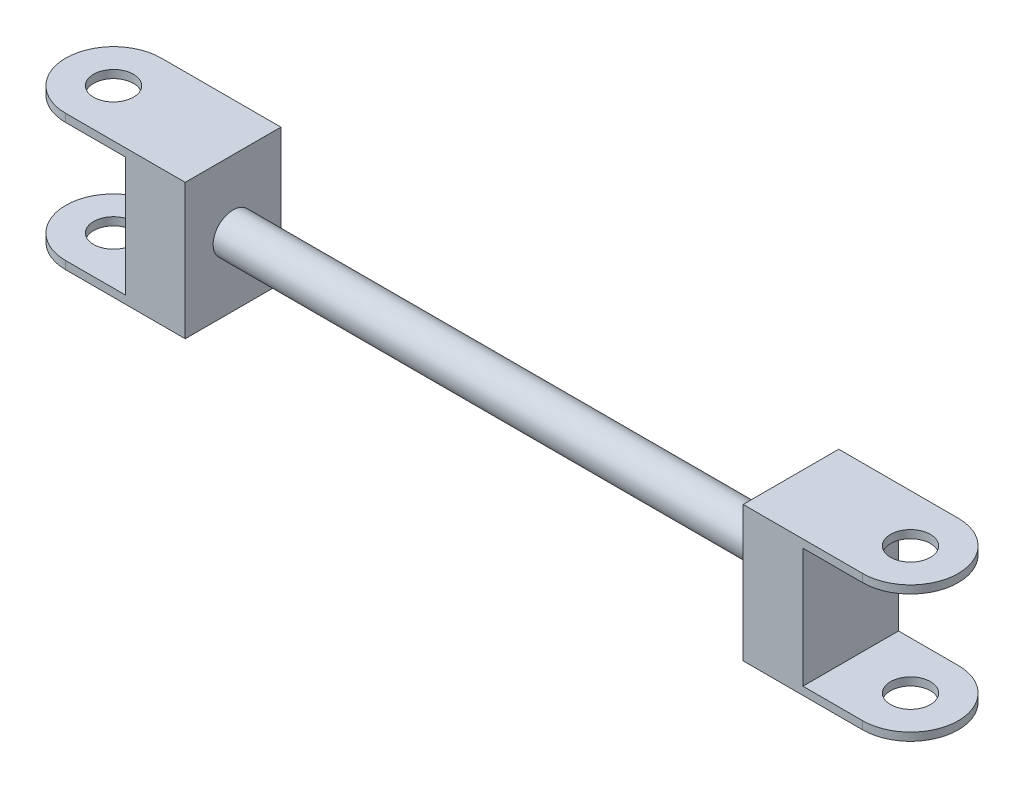
SolidWorks part; units mm, degrees
ref_plane "Front Plane" through (0, 0, 0) normal (0, 0, 1) x (1, 0, 0)
ref_plane "Top Plane" through (0, 0, 0) normal (0, 1, 0) x (1, 0, 0)
ref_plane "Right Plane" through (0, 0, 0) normal (1, 0, 0) x (0, 0, -1)
sketch "Sketch1" plane through (0, 0, 0) normal (0, 1, 0) x (1, 0, 0)
  line L1 (-69.1768, 12) -> (-39.1768, 12)
  line L3 (-69.1768, -12) -> (-39.1768, -12)
  line L4 (-39.1768, 12) -> (-39.1768, -12)
  line L5 (130.8232, 12) -> (100.8232, 12)
  line L7 (130.8232, -12) -> (100.8232, -12)
  line L8 (100.8232, 12) -> (100.8232, -12)
  circle A0 centre (-69.1768, 0) radius 5
  circle A1 centre (130.8232, 0) radius 5
  arc A2 (-69.1768, 12) -> (-69.1768, -12) centre (-69.1768, 0) ccw
  arc A3 (130.8232, -12) -> (130.8232, 12) centre (130.8232, 0) ccw
  dimension "D2" = 10
  dimension "D3" = 10
  dimension "D4" = 24
  dimension "D5" = 24
  dimension "D8" = 30
  dimension "D1" = 200
  dimension "D6" = 30
  dimension "D7" = 24
extrude "Boss-Extrude1" add sketch "Sketch1" along normal blind 17 and the other way blind 17 contours A2 L1 L4 L3 | A3 L5 L8 L7 | A0 | A1
sketch "Sketch3" plane through (-39.1768, 0, 0) normal (1, 0, 0) x (0, 0, -1)
  circle A0 centre (0, 0) radius 5
  dimension "D1" = 10
extrude "Boss-Extrude2" add sketch "Sketch3" along normal up to surface (140 mm away) up to face at (100.8232, 0, 0)
sketch "Sketch4" plane through (0, 0, 0) normal (0, 1, 0) x (1, 0, 0)
  line L0 (100.8232, -12) -> (130.8232, -12) construction
  line L1 (130.8232, 12) -> (100.8232, 12) construction
  line L3 (-69.1768, -12) -> (-39.1768, -12) construction
  line L5 (-39.1768, 12) -> (-69.1768, 12) construction
  line L6 (115.8232, -12) -> (130.8232, -12)
  line L7 (130.8232, 12) -> (115.8232, 12)
  line L9 (-69.1768, -12) -> (-54.1768, -12)
  line L11 (-54.1768, 12) -> (-69.1768, 12)
  line L12 (115.8232, 12) -> (115.8232, -12)
  line L13 (-54.1768, 12) -> (-54.1768, -12)
  arc A0 (130.8232, -12) -> (130.8232, 12) centre (130.8232, 0) ccw construction
  arc A1 (-69.1768, 12) -> (-69.1768, -12) centre (-69.1768, 0) ccw construction
  arc A2 (130.8232, -12) -> (130.8232, 12) centre (130.8232, 0) ccw
  arc A3 (-69.1768, 12) -> (-69.1768, -12) centre (-69.1768, 0) ccw
  dimension "D1" = 15
  dimension "D2" = 15
extrude "Cut-Extrude1" cut sketch "Sketch4" against normal blind 15 and the other way blind 15
